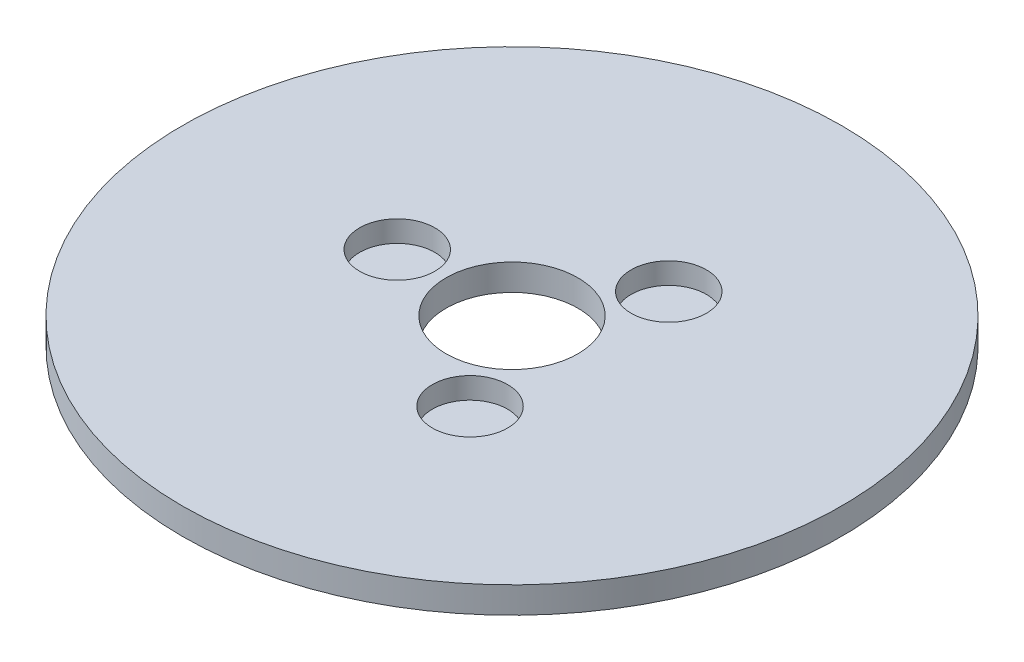
SolidWorks part; units mm, degrees
ref_plane "Front Plane" through (0, 0, 0) normal (0, 0, 1) x (1, 0, 0)
ref_plane "Top Plane" through (0, 0, 0) normal (0, 1, 0) x (1, 0, 0)
ref_plane "Right Plane" through (0, 0, 0) normal (1, 0, 0) x (0, 0, -1)
sketch "Sketch1" plane through (0, 0, 0) normal (0, 1, 0) x (1, 0, 0)
  circle A0 centre (0, 0) radius 87.5
  dimension "FLANGE_OD" = 175
extrude "Boss-Extrude1" add sketch "Sketch1" along normal blind 7
sketch "Sketch2" plane through (0, 0, 0) normal (0, 1, 0) x (1, 0, 0)
  circle A0 centre (0, 0) radius 17.5
  dimension "BORE_D" = 35
extrude "Cut-Extrude1" cut sketch "Sketch2" along normal through all
sketch "Sketch3" plane through (0, 7, 0) normal (0, 1, 0) x (1, 0, 0)
  circle A0 centre (0, 0) radius 30.4701 construction
  circle A1 centre (-30.4701, 0) radius 10
  dimension "BOLT_D" = 20
  dimension "BOLT_PCD" = 60.9402
extrude "Cut-Extrude2" cut sketch "Sketch3" against normal blind 5.6608
pattern_circular "CirPattern1" count 3 over 360 about axis through (0, 0, 0) along (0, 1, 0) of "Cut-Extrude2"
